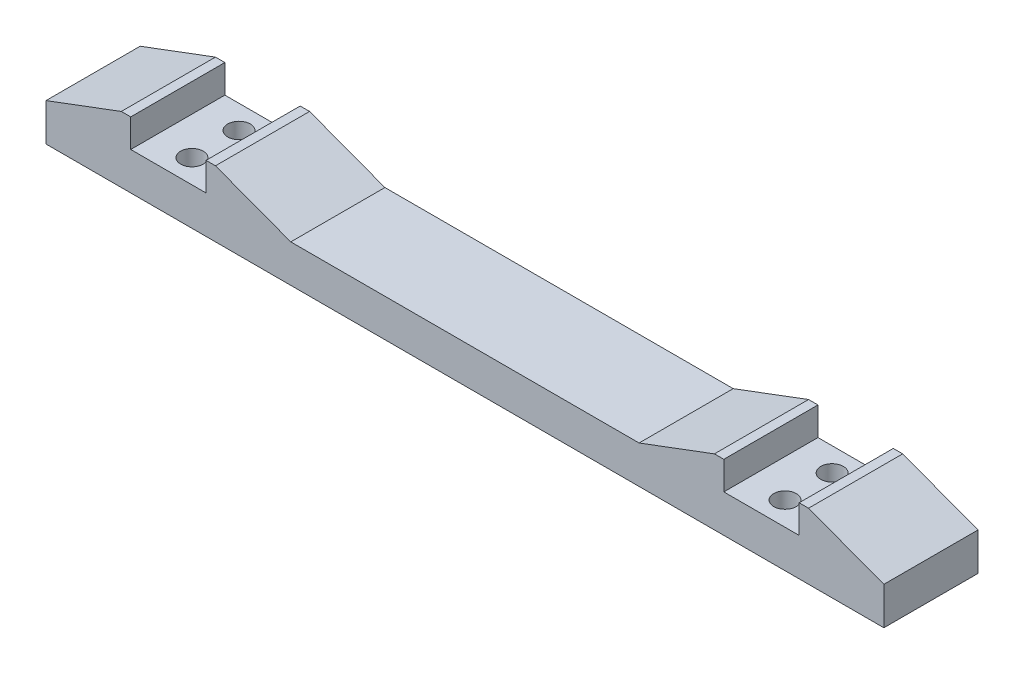
SolidWorks part; units mm, degrees
other "标注1"
sketch "草图3" plane through (-22.25, 4, -10) normal (-0.231, 0.6469, -0.7268) x (-0.9696, -0.2151, 0.1167)
ref_plane "前视基准面" through (0, 0, 0) normal (0, 0, 1) x (1, 0, 0)
ref_plane "上视基准面" through (0, 0, 0) normal (0, 1, 0) x (1, 0, 0)
ref_plane "右视基准面" through (0, 0, 0) normal (1, 0, 0) x (0, 0, -1)
other "Configuration Table"
sketch "草图4" plane through (0, 0, 0) normal (0, 0, 1) x (1, 0, 0)
  line L6 (8.5, -1.5) -> (17.75, -1.5)
  line L11 (17.75, -1.5) -> (17.75, -3.5)
  line L16 (17.75, -3.5) -> (-4.5, -3.5)
  line L17 (-4.5, -3.5) -> (-4.5, -1.5)
  line L19 (0, 0) -> (0, -1.5)
  line L20 (0, -1.5) -> (4, -1.5)
  line L21 (4, -1.5) -> (4, 0)
  line L26 (4, 0) -> (4.5, 0)
  line L27 (4.5, 0) -> (8.5, -1.5)
  line L28 (0, 0) -> (-0.5, 0)
  line L29 (-0.5, 0) -> (-4.5, -1.5)
  dimension "D2" = 4
  dimension "D4" = 0.5
  dimension "D5" = 2
  dimension "D6" = 2
  dimension "D7" = 4
  dimension "D8" = 1.5
  dimension "D9" = 4
  dimension "D10" = 22.25
extrude "凸台-拉伸1" add sketch "草图4" along normal blind 2.5 contours L28 L29 L17 L16 L11 L6 L27 L26 L21 L20 L19 | L19 | L21 region at (5.9579, -2.2764, 0)
sketch "草图5" plane through (0, -1.5, 0) normal (0, 1, 0) x (1, 0, 0)
  line L0 (0, 0) -> (4, -2.5) construction
  line L1 (0, -2.5) -> (0, 0) construction
  line L2 (0, -2.5) -> (4, -2.5) construction
  line L3 (4, -2.5) -> (4, 0) construction
  line L4 (0, 0) -> (4, 0) construction
  circle A0 centre (2, -1.25) radius 0.6
  circle A1 centre (2, -1.25) radius 1
  dimension "D1" = 1.2
  dimension "D2" = 2
extrude "切除-拉伸1" cut sketch "草图5" against normal through all contours A0
extrude "切除-拉伸2" cut sketch "草图5<3>" along normal blind 1 from surface contours A1 starting at face at (2, -3.5, 1.85)
sketch "草图5<3>" plane through (0, -1.5, 0) normal (0, 1, 0) x (1, 0, 0) same geometry as "草图5"
mirror "镜向1" about plane through (0, 0, 2.5) normal (0, 0, 1) of bodies 215 203
mirror "镜向2" about plane through (17.75, 0, 2.5) normal (1, 0, 0) of bodies 204
